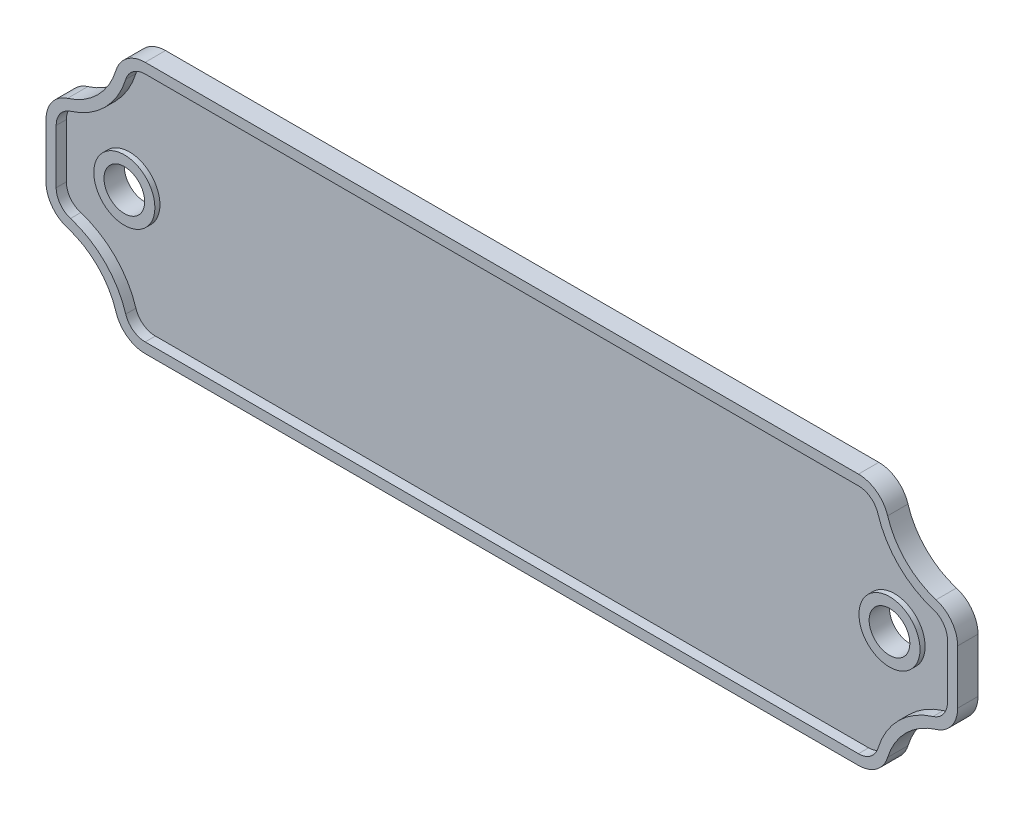
SolidWorks part; units mm, degrees
material "Brass"
ref_plane "Front Plane" through (0, 0, 0) normal (0, 0, 1) x (1, 0, 0)
ref_plane "Top Plane" through (0, 0, 0) normal (0, 1, 0) x (1, 0, 0)
ref_plane "Right Plane" through (0, 0, 0) normal (1, 0, 0) x (0, 0, -1)
sketch "Sketch1" plane through (0, 0, 0) normal (0, 0, 1) x (1, 0, 0)
  line L0 (-56, 3.3139) -> (-56, -3.3139)
  line L4 (-56, -15.5) -> (-56, 15.5) construction
  line L5 (0, 15.5) -> (0, -15.5) construction
  line L6 (-47, 0) -> (-56, 0) construction
  line L7 (-43.8139, 15.5) -> (0, 15.5)
  line L9 (0, -15.5) -> (-43.8139, -15.5)
  line L10 (-47, 0) -> (0, 0) construction
  line L15 (0, -14.25) -> (-43.8139, -14.25)
  line L16 (-54.75, 3.3139) -> (-54.75, -3.3139)
  line L17 (-43.8139, 14.25) -> (0, 14.25)
  line L18 (47, 0) -> (0, 0) construction
  line L19 (47, 0) -> (56, 0) construction
  line L20 (56, -15.5) -> (56, 15.5) construction
  line L21 (43.8139, 14.25) -> (0, 14.25)
  line L22 (54.75, 3.3139) -> (54.75, -3.3139)
  line L23 (0, -14.25) -> (43.8139, -14.25)
  line L24 (0, -15.5) -> (43.8139, -15.5)
  line L25 (43.8139, 15.5) -> (0, 15.5)
  line L26 (56, 3.3139) -> (56, -3.3139)
  arc A0 (-53.3529, 6.8981) -> (-47.3981, 12.8529) centre (-56, 15.5) ccw
  arc A3 (-53.3529, -6.8981) -> (-47.3981, -12.8529) centre (-56, -15.5) cw
  circle A4 centre (-47, 0) radius 2.5
  circle A7 centre (-47, 0) radius 3.75
  arc A12 (-47.3981, -12.8529) -> (-43.8139, -15.5) centre (-43.8139, -11.75) ccw
  arc A13 (-53.3529, -6.8981) -> (-56, -3.3139) centre (-52.25, -3.3139) cw
  arc A14 (-53.3529, 6.8981) -> (-56, 3.3139) centre (-52.25, 3.3139) ccw
  arc A15 (-47.3981, 12.8529) -> (-43.8139, 15.5) centre (-43.8139, 11.75) cw
  arc A16 (-46.2034, -12.4853) -> (-43.8139, -14.25) centre (-43.8139, -11.75) ccw
  arc A17 (-52.9853, -5.7034) -> (-46.2034, -12.4853) centre (-56, -15.5) cw
  arc A18 (-52.9853, -5.7034) -> (-54.75, -3.3139) centre (-52.25, -3.3139) cw
  arc A19 (-52.9853, 5.7034) -> (-54.75, 3.3139) centre (-52.25, 3.3139) ccw
  arc A20 (-52.9853, 5.7034) -> (-46.2034, 12.4853) centre (-56, 15.5) ccw
  arc A21 (-46.2034, 12.4853) -> (-43.8139, 14.25) centre (-43.8139, 11.75) cw
  arc A22 (46.2034, 12.4853) -> (43.8139, 14.25) centre (43.8139, 11.75) ccw
  arc A23 (52.9853, 5.7034) -> (46.2034, 12.4853) centre (56, 15.5) cw
  arc A24 (52.9853, 5.7034) -> (54.75, 3.3139) centre (52.25, 3.3139) cw
  arc A25 (52.9853, -5.7034) -> (54.75, -3.3139) centre (52.25, -3.3139) ccw
  arc A26 (52.9853, -5.7034) -> (46.2034, -12.4853) centre (56, -15.5) ccw
  arc A27 (46.2034, -12.4853) -> (43.8139, -14.25) centre (43.8139, -11.75) cw
  arc A28 (47.3981, 12.8529) -> (43.8139, 15.5) centre (43.8139, 11.75) ccw
  arc A29 (53.3529, 6.8981) -> (56, 3.3139) centre (52.25, 3.3139) cw
  arc A30 (53.3529, -6.8981) -> (56, -3.3139) centre (52.25, -3.3139) ccw
  arc A31 (47.3981, -12.8529) -> (43.8139, -15.5) centre (43.8139, -11.75) cw
  circle A32 centre (47, 0) radius 3.75
  circle A33 centre (47, 0) radius 2.5
  arc A34 (53.3529, -6.8981) -> (47.3981, -12.8529) centre (56, -15.5) ccw
  arc A35 (53.3529, 6.8981) -> (47.3981, 12.8529) centre (56, 15.5) cw
  point P8 (-56, 0)
  point P20 (-56, -6.5)
  point P24 (-56, 6.5)
  point P67 (56, 6.5)
  point P70 (56, -6.5)
  dimension "D7" = 3.75
  dimension "D3" = 31
  dimension "D4" = 1.25
  dimension "D6" = 9
extrude "Boss-Extrude1" add sketch "Sketch1" along normal blind 2.5 contours A29 A35 A28 L25 L7 A15 A0 A14 L0 A13 A3 A12 L9 L24 A31 A34 A30 L26 A26 A27 L23 L15 A16 A17 A18 L16 A19 A20 A21 L17 L21 A22 A23 A24 L22 A25 region at (-54.3317, 4.8514, 0)
extrude "Boss-Extrude2" add sketch "Sketch1<3>" along normal blind 1.25 contours A17 A7 region at (0, 0, 0)
sketch "Sketch1<3>" plane through (0, 0, 0) normal (0, 0, 1) x (1, 0, 0) same geometry as "Sketch1"
extrude "Boss-Extrude4" add sketch "Sketch1<4>" along normal offset from surface 0.625 and the other way offset from surface 0.625 contours A7 A4 | A32 A33 region at (-50.6439, 0, 0) region at (43.3561, 0, 0) up to face at (-43.25, 0, 1.25) offset beyond the face yes other way up to face at (0, 0, 0)
sketch "Sketch1<4>" plane through (0, 0, 0) normal (0, 0, 1) x (1, 0, 0) same geometry as "Sketch1"
equation "\"A\"= 1.25mm"
equation "\"D4@Sketch1\"=\"A\""
equation "\"D1@Boss-Extrude1\"=\"A\"*2"
equation "\"D1@Boss-Extrude2\"=\"A\""
equation "\"D8@Sketch1\"=\"A\""
equation "\"B\"= 112mm"
equation "\"D2@Sketch1\"=\"B\""
equation "\"D1@Boss-Extrude4\"=\"A\"/2"
equation "\"D2@Boss-Extrude4\"=\"A\"/2"
